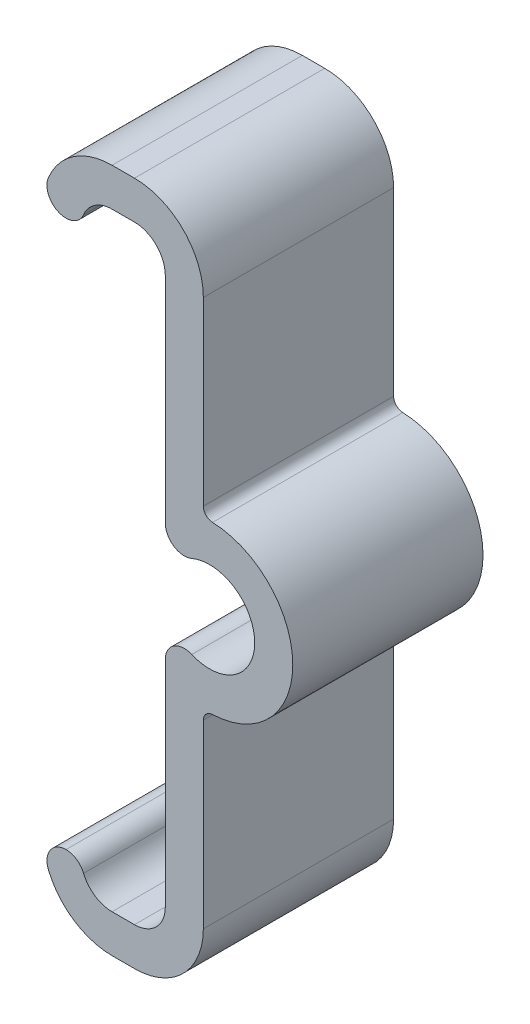
SolidWorks part; units mm, degrees
ref_plane "Front Plane" through (0, 0, 0) normal (0, 0, 1) x (1, 0, 0)
ref_plane "Top Plane" through (0, 0, 0) normal (0, 1, 0) x (1, 0, 0)
ref_plane "Right Plane" through (0, 0, 0) normal (1, 0, 0) x (0, 0, -1)
sketch "Sketch1" plane through (0, 0, 0) normal (0, 0, 1) x (1, 0, 0)
  line L0 (-4.318, -11.285) -> (-4.318, -14.37) construction
  line L1 (-2.748, -15.94) -> (-1.57, -15.94) construction
  line L2 (0, -14.37) -> (0, 14.37) construction
  line L3 (-1.57, 15.94) -> (-2.748, 15.94) construction
  line L4 (-4.318, 14.37) -> (-4.318, 11.285) construction
  line L5 (-4.368, -11.285) -> (-4.368, -14.37)
  line L6 (-2.748, -15.99) -> (-1.57, -15.99)
  line L7 (0.05, -14.37) -> (0.05, 14.37)
  line L8 (-1.57, 15.99) -> (-2.748, 15.99)
  line L9 (-4.368, 14.37) -> (-4.368, 11.285)
  line L10 (-6.368, -11.285) -> (-6.368, -14.37)
  line L11 (-2.748, -17.99) -> (-1.57, -17.99)
  line L12 (2.05, -14.37) -> (2.05, 14.37)
  line L13 (-1.57, 17.99) -> (-2.748, 17.99)
  line L14 (-6.368, 14.37) -> (-6.368, 11.285)
  line L15 (-4.368, 14.37) -> (-6.368, 14.37)
  line L16 (-4.368, -14.37) -> (-6.368, -14.37)
  arc A0 (-4.318, -14.37) -> (-2.748, -15.94) centre (-2.748, -14.37) ccw construction
  arc A1 (-1.57, -15.94) -> (0, -14.37) centre (-1.57, -14.37) ccw construction
  arc A2 (0, 14.37) -> (-1.57, 15.94) centre (-1.57, 14.37) ccw construction
  arc A3 (-2.748, 15.94) -> (-4.318, 14.37) centre (-2.748, 14.37) ccw construction
  arc A4 (-4.368, -14.37) -> (-2.748, -15.99) centre (-2.748, -14.37) ccw
  arc A5 (-1.57, -15.99) -> (0.05, -14.37) centre (-1.57, -14.37) ccw
  arc A6 (0.05, 14.37) -> (-1.57, 15.99) centre (-1.57, 14.37) ccw
  arc A7 (-2.748, 15.99) -> (-4.368, 14.37) centre (-2.748, 14.37) ccw
  circle A8 centre (2.375, 0) radius 2.375
  circle A9 centre (2.375, 0) radius 4.375
  arc A10 (-6.368, -14.37) -> (-2.748, -17.99) centre (-2.748, -14.37) ccw
  arc A11 (-1.57, -17.99) -> (2.05, -14.37) centre (-1.57, -14.37) ccw
  arc A12 (2.05, 14.37) -> (-1.57, 17.99) centre (-1.57, 14.37) ccw
  arc A13 (-2.748, 17.99) -> (-6.368, 14.37) centre (-2.748, 14.37) ccw
  dimension "D2" = 4.75
  dimension "D3" = 2.375
  dimension "D1" = 0.05
  dimension "D4" = 2
  dimension "D5" = 2
extrude "Boss-Extrude1" add sketch "Sketch1" along normal blind 10 contours L13 A13 L15 A7 L8 A6 L7 A9 L12 A12 | L12 A9 L7 A8 | L12 A9 A8 | L7 A9 L12 A8 | L11 A11 L12 A9 L7 A5 L6 A4 L16 A10 region at (-2.159, -16.1558, 0) region at (0.9826, -2.9314, 0) region at (0.9826, 2.9314, 0) region at (0.2158, 9.038, 0) region at (2.1493, -3.3578, 0)
fillet "Fillet1" radius 1 2 edges at (0.05, -0.4848, 5) (0.05, 0.4848, 5)
fillet "Fillet2" radius 0.5 2 edges at (2.05, -4.3629, 5) (2.05, 4.3629, 5)
fillet "Fillet3" radius 1 4 edges at (-6.368, 14.37, 5) (-4.368, 14.37, 5) (-6.368, -14.37, 5) (-4.368, -14.37, 5)
equation "\"D3@Sketch1\"=\"D2@Sketch1\"/2"
